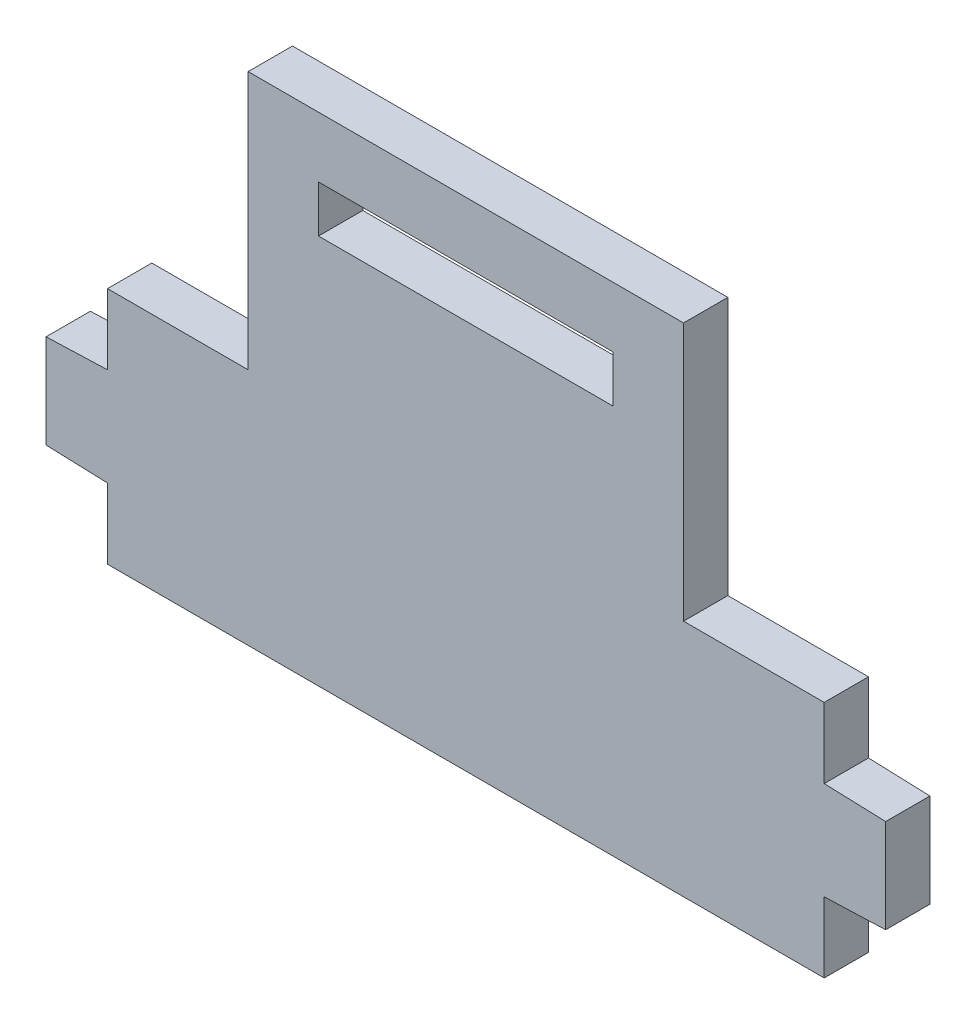
SolidWorks part; units mm, degrees
ref_plane "Front Plane" through (0, 0, 0) normal (0, 0, 1) x (1, 0, 0)
ref_plane "Top Plane" through (0, 0, 0) normal (0, 1, 0) x (1, 0, 0)
ref_plane "Right Plane" through (0, 0, 0) normal (1, 0, 0) x (0, 0, -1)
ref_plane "Plane1" through (0, 0, 2.54) normal (0, 0, -1) x (-1, 0, 0)
ref_plane "Plane2" through (0, 0, 8.54) normal (0, 0, -1) x (-1, 0, 0)
ref_axis "Axis1" through (-48.5353, 209.7215, 2.54) along (0, 1, 0)
ref_axis "Axis2" through (48.5353, 44.5, 2.54) along (0, 1, 0)
ref_axis "Axis3" through (56.8598, 204.4993, 8.54) along (0, 1, 0)
ref_axis "Axis4" through (-56.8598, 212.1673, 8.54) along (0, -1, 0)
sketch "Sketch1" plane through (0, 0, 2.54) normal (0, 0, -1) x (-1, 0, 0)
  line L0 (48.5353, -833.3102) -> (48.5353, 49166.6898) construction
  line L1 (56.8598, -832.8475) -> (56.8598, 49167.1525) construction
  line L2 (-56.8598, -832.819) -> (-56.8598, 49167.181) construction
  line L3 (-48.5353, -833.1972) -> (-48.5353, 49166.8028) construction
  line L4 (48.5353, 209.7215) -> (48.5353, 217.1537) construction
  line L5 (-48.5353, 44.5) -> (-48.5353, 223.6714) construction
  line L6 (-56.8598, 204.4993) -> (-56.8598, 219.7756) construction
  line L8 (56.8598, 212.1673) -> (56.8598, 191.1029) construction
  line L9 (-48.5353, 182.1653) -> (-56.8598, 182.456)
  line L10 (-56.8598, 182.456) -> (-56.8598, 195.156)
  line L11 (-56.8598, 195.156) -> (-48.5353, 195.4467)
  line L12 (-48.5353, 195.4467) -> (-48.5353, 204.9717)
  line L13 (-48.5353, 204.9717) -> (-29.4853, 204.9717)
  line L14 (-29.4853, 204.9717) -> (-29.4853, 239.9538)
  line L15 (-48.5353, 182.1653) -> (-48.5353, 172.6403)
  line L16 (-48.5353, 172.6403) -> (48.5353, 172.6403)
  line L17 (48.5353, 172.6403) -> (48.5353, 182.1653)
  line L18 (48.5353, 182.1653) -> (56.8598, 182.456)
  line L19 (56.8598, 182.456) -> (56.8598, 195.156)
  line L20 (56.8598, 195.156) -> (48.5353, 195.4467)
  line L21 (48.5353, 195.4467) -> (48.5353, 204.9717)
  line L22 (48.5353, 204.9717) -> (29.4853, 204.9717)
  line L23 (29.4853, 204.9717) -> (29.4853, 239.9538)
  line L24 (29.4853, 239.9538) -> (-29.4853, 239.9538)
  line L26 (-48.3211, 210.0517) -> (-54.0132, 210.0517) construction
  line L27 (-1049.2698, 228.6) -> (48950.7302, 228.6) construction
  line L28 (-19.9603, 231.775) -> (19.9603, 231.775)
  line L29 (-19.9603, 231.775) -> (-19.9603, 225.425)
  line L30 (-19.9603, 225.425) -> (19.9603, 225.425)
  line L31 (19.9603, 231.775) -> (19.9603, 225.425)
  line L32 (0, 231.775) -> (0, 239.9538) construction
  ellipse E0 centre (-49.2698, 228.6) end of major axis (-49.2698, 230.4288) minor radius 0.5783 construction
  ellipse E1 centre (-49.2698, 228.6) end of major axis (-49.2698, 230.4288) minor radius 0.5783 construction
  point P49 (-19.9603, 228.6)
  point P55 (0, 239.9538)
  dimension "D1" = 9.525
  dimension "D2" = 19.05
  dimension "D3" = 12.7
  dimension "D4" = 92
  dimension "D5" = 9.525
  dimension "D6" = 5.08
  dimension "D7" = 6.35
  dimension "D8" = 9.525
extrude "Boss-Extrude1" add sketch "Sketch1" against normal blind 6
